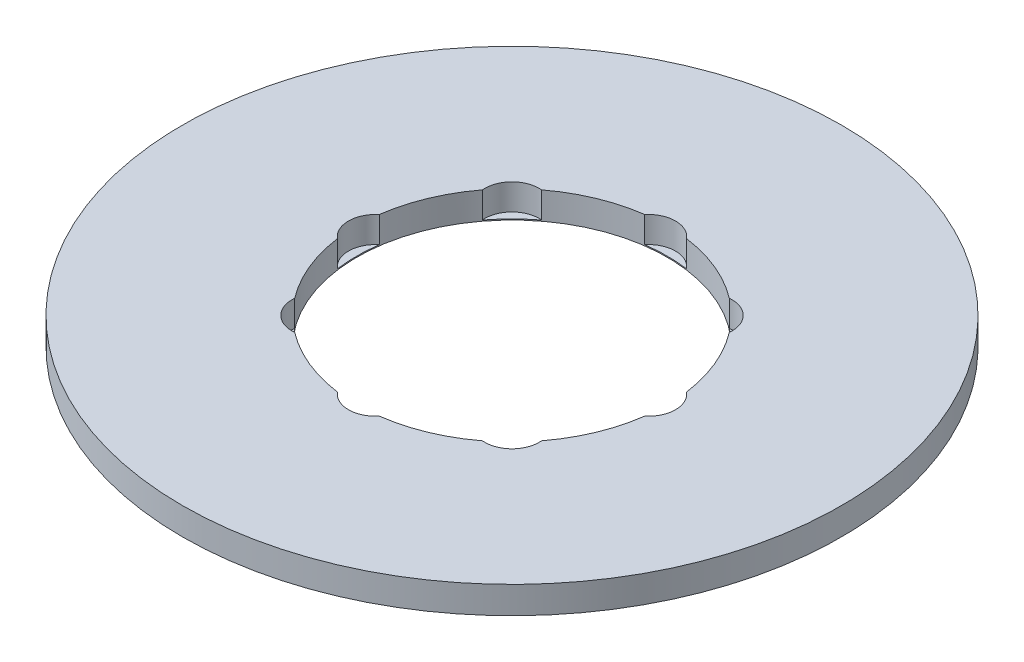
SolidWorks part; units mm, degrees
ref_plane "Front Plane" through (0, 0, 0) normal (0, 0, 1) x (1, 0, 0)
ref_plane "Top Plane" through (0, 0, 0) normal (0, 1, 0) x (1, 0, 0)
ref_plane "Right Plane" through (0, 0, 0) normal (1, 0, 0) x (0, 0, -1)
sketch "Sketch1" plane through (0, 0, 0) normal (0, 1, 0) x (1, 0, 0)
  circle A0 centre (0, 0) radius 85
  dimension "FLANGE_OD" = 170
extrude "Boss-Extrude1" add sketch "Sketch1" along normal blind 7
sketch "Sketch2" plane through (0, 0, 0) normal (0, 1, 0) x (1, 0, 0)
  circle A0 centre (0, 0) radius 40
  dimension "BORE_D" = 80
extrude "Cut-Extrude1" cut sketch "Sketch2" along normal through all
sketch "Sketch3" plane through (0, 7, 0) normal (0, 1, 0) x (1, 0, 0)
  circle A0 centre (0, 0) radius 35.1661 construction
  circle A1 centre (-35.1661, 0) radius 7.0058
  dimension "BOLT_D" = 14.0117
  dimension "BOLT_PCD" = 70.3322
extrude "Cut-Extrude2" cut sketch "Sketch3" against normal blind 6.7292
pattern_circular "CirPattern1" count 8 over 360 about axis through (0, 0, 0) along (0, 1, 0) of "Cut-Extrude2"
